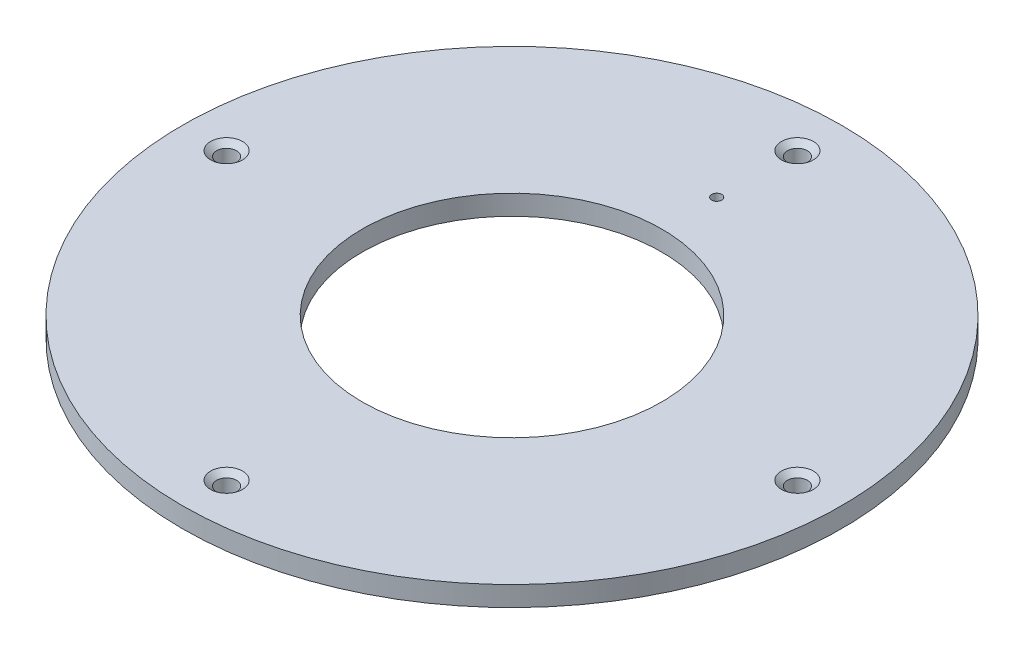
SolidWorks part; units mm, degrees
material "1060 Alloy"
ref_plane "Front Plane" through (0, 0, 0) normal (0, 0, 1) x (1, 0, 0)
ref_plane "Top Plane" through (0, 0, 0) normal (0, 1, 0) x (1, 0, 0)
ref_plane "Right Plane" through (0, 0, 0) normal (1, 0, 0) x (0, 0, -1)
sketch "Sketch1" plane through (0, 0, 0) normal (0, 1, 0) x (1, 0, 0)
  circle A0 centre (0, 0) radius 16.5
  dimension "D1" = 33
extrude "Boss-Extrude1" add sketch "Sketch1" along normal blind 1
sketch "Sketch2" plane through (0, 1, 0) normal (0, 1, 0) x (1, 0, 0)
  circle A0 centre (0, 0) radius 7.5
  dimension "D1" = 15
extrude "Cut-Extrude1" cut sketch "Sketch2" against normal through all both and the other way through all
ref_plane "Plane2" through (0, 0.5, 0) normal (0, 1, 0) x (1, 0, 0)
sketch "Sketch4" plane through (0, 1, 0) normal (0, 1, 0) x (1, 0, 0)
  circle A0 centre (0, 10.25) radius 0.25
  dimension "D1" = 0.5
  dimension "D2" = 10.25
extrude "Cut-Extrude2" cut sketch "Sketch4" against normal through all both and the other way through all
hole_wizard "CSK for M2 Flat Head Machine Screw1" positions "Sketch5" profile "Sketch6" countersink size "M2" standard "ANSI Metric" end condition through all
sketch "Sketch5" plane through (0, 1, 0) normal (0, 1, 0) x (1, 0, 0)
  point P0 (0, 14.29)
  point P2 (14.29, 0)
  point P4 (0, -14.29)
  point P6 (-14.29, 0)
  dimension "D1" = 14.29
  dimension "D2" = 14.29
  dimension "D3" = 14.29
  dimension "D4" = 14.29
sketch "Sketch6" plane through (0, 1, -14.29) normal (1, 0, 0) x (0, 0, 1)
  line L0 (0, 0) -> (0, 1)
  line L1 (0, 1) -> (0.5, 1)
  line L2 (0.5, 1) -> (0.5, 0.2517)
  line L3 (0.5, 0.2517) -> (0.8, 0)
  line L5 (0.8, 0) -> (0, 0)
  line L6 (-0.5, 0.2517) -> (-0.8, 0) construction
  line L11 (0, -6.35) -> (0, 107.95) construction
  dimension "Thru Hole Dia." = 1
  dimension "Thru Hole Depth" = 1
  dimension "Near C'Sink Dia." = 1.6
  dimension "Near C'Sink Angle" = 100
